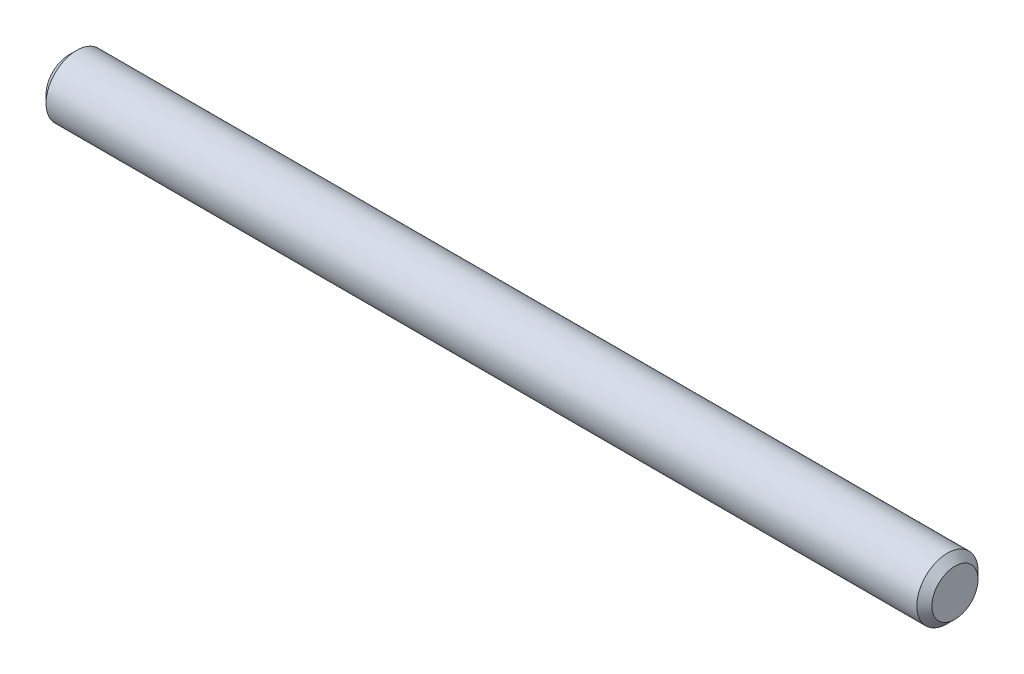
SolidWorks part; units mm, degrees
ref_plane "Front Plane" through (0, 0, 0) normal (0, 0, 1) x (1, 0, 0)
ref_plane "Top Plane" through (0, 0, 0) normal (0, 1, 0) x (1, 0, 0)
ref_plane "Right Plane" through (0, 0, 0) normal (1, 0, 0) x (0, 0, -1)
sketch "Sketch1" plane through (0, 0, 0) normal (0, 0, 1) x (1, 0, 0)
  line L0 (-34.925, 0) -> (34.925, 0) construction
  line L1 (34.925, 2.413) -> (34.925, -2.413) construction
  line L2 (-34.925, 2.413) -> (-34.925, -2.413) construction
  point P6 (32.1469, -2.413)
  dimension "Thread Diameter" = 4.826
  dimension "Length" = 69.85
  dimension "D1" = 2.7781
sketch "Sketch2" plane through (0, 0, 0) normal (1, 0, 0) x (0, 0, -1)
  circle A0 centre (0, 0) radius 2.413
extrude "Boss-Extrude1" add sketch "Sketch2" against normal up to vertex (34.925 mm away) and the other way up to vertex (34.925 mm away) up to point (-34.925, 0, 0) other way up to point (34.925, 0, 0)
cosmetic thread "Cosmetic Thread1" parameters "D2"=3.8811
sketch "Sketch3" plane through (34.925, 0, 0) normal (1, 0, 0) x (0, 0, -1)
  circle A1 centre (0, 0) radius 2.413
  circle A2 centre (0, 0) radius 2.413
  dimension "D1" = 0
curve "Helix/Spiral1" pitch 0.7937 height 70.6437 turns 89 parameters "Pitch"=0.7937
chamfer "Chamfer1" distance 0.5953 angle 45 2 edges at (-34.925, 0, -2.413) (34.925, 0, -2.413)
sketch "Sketch4" plane through (0, 0, 0) normal (0, 0, 1) x (1, 0, 0)
  line L0 (34.8754, 2.4989) -> (35.2723, 1.8115) construction
  line L1 (35.2723, 1.8115) -> (35.6691, 2.4989) construction
  line L2 (35.6691, 2.4989) -> (34.8754, 2.4989) construction
  line L3 (35.2723, 2.4989) -> (35.2723, 2.413) construction
  line L4 (35.2723, 1.8115) -> (35.2723, 1.8974) construction
  line L5 (35.2227, 1.8974) -> (35.3219, 1.8974) construction
  line L6 (34.925, 2.413) -> (35.6195, 2.413) construction
  line L7 (35.2227, 1.8974) -> (34.9002, 2.456)
  line L8 (35.2227, 1.8974) -> (35.3219, 1.8974)
  line L9 (34.9002, 2.456) -> (35.6443, 2.456)
  line L10 (35.6443, 2.456) -> (35.3219, 1.8974)
  point P13 (35.2723, 2.456)
  dimension "D2" = 0.0992
sweep "Cut-Sweep3" [suppressed] cut profiles "Sketch4" path "Helix/Spiral1"
equation "\"D3@Helix/Spiral1\" = \"Length@Sketch1\"+\"Pitch@Helix/Spiral1\""
equation "\"D1@Chamfer1\" = \"Pitch@Helix/Spiral1\"*.75"
equation "\"D1@Sketch4\" = \"Pitch@Helix/Spiral1\""
equation "\"D2@Sketch4\" = \"D1@Sketch4\"/8"
equation "\"D1@Sketch1\" = \"Pitch@Helix/Spiral1\"*3.50"
